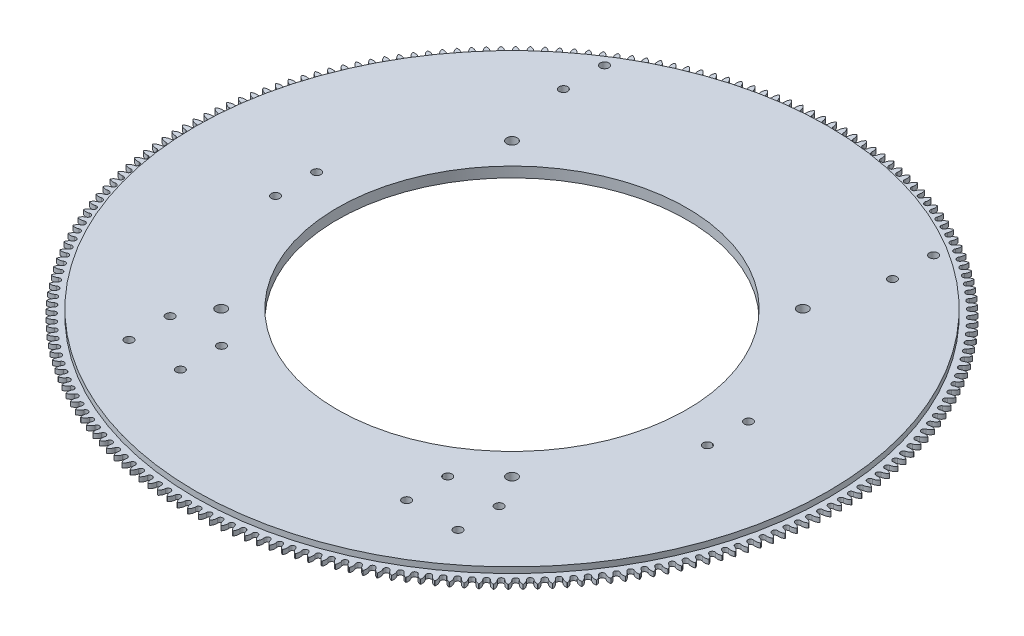
SolidWorks part; units mm, degrees
material "PC High Viscosity"
ref_plane "Front Plane" through (0, 0, 0) normal (0, 0, 1) x (1, 0, 0)
ref_plane "Top Plane" through (0, 0, 0) normal (0, 1, 0) x (1, 0, 0)
ref_plane "Right Plane" through (0, 0, 0) normal (1, 0, 0) x (0, 0, -1)
sketch "Sketch1" plane through (0, 0, 0) normal (0, 1, 0) x (1, 0, 0)
  line L0 (0, 0) -> (0, -95.25) construction
  line L1 (0, -95.25) -> (82.55, -95.25) construction
  line L2 (82.55, -95.25) -> (82.55, -146.0008) construction
  line L3 (82.55, -95.25) -> (88.9, -95.25) construction
  line L4 (88.9, -95.25) -> (88.9, -146.0008) construction
  line L5 (69.85, -109.5375) -> (69.85, -134.9375) construction
  line L6 (101.6, -109.5375) -> (101.6, -134.9375) construction
  line L7 (69.85, -109.5375) -> (101.6, -109.5375) construction
  line L8 (0, 0) -> (89.8026, -89.8026) construction
  line L9 (0, 0) -> (0, 133.35) construction
  line L10 (0, 133.35) -> (101.6, 133.35) construction
  line L11 (101.6, 133.35) -> (101.6, 158.75) construction
  line L12 (0, 0) -> (89.8026, 89.8026) construction
  line L13 (0, 0) -> (133.35, 0) construction
  line L14 (133.35, 0) -> (133.35, -12.7) construction
  line L15 (133.35, 0) -> (133.35, 12.7) construction
  line L16 (101.6, -134.9375) -> (118.4058, -157.2577) construction
  line L17 (101.6, -134.9375) -> (0, 0) construction
  circle A0 centre (0, 0) radius 107.95
  circle A1 centre (69.85, -109.5375) radius 2.6289
  circle A2 centre (69.85, -134.9375) radius 2.6289
  circle A3 centre (101.6, -109.5375) radius 2.6289
  circle A4 centre (101.6, -134.9375) radius 2.6289
  circle A5 centre (89.8026, -89.8026) radius 3.2639
  circle A6 centre (101.6, 133.35) radius 2.6289
  circle A7 centre (101.6, 158.75) radius 2.6289
  circle A10 centre (89.8026, 89.8026) radius 3.2639
  circle A11 centre (133.35, -12.7) radius 2.6289
  circle A12 centre (133.35, 12.7) radius 2.6289
  circle A13 centre (0, 0) radius 196.85
  circle A14 centre (-69.85, -134.9375) radius 2.6289
  circle A15 centre (-101.6, -134.9375) radius 2.6289
  circle A16 centre (-101.6, -109.5375) radius 2.6289
  circle A17 centre (-89.8026, -89.8026) radius 3.2639
  circle A18 centre (-69.85, -109.5375) radius 2.6289
  circle A19 centre (-133.35, -12.7) radius 2.6289
  circle A20 centre (-133.35, 12.7) radius 2.6289
  circle A21 centre (-89.8026, 89.8026) radius 3.2639
  circle A22 centre (-101.6, 158.75) radius 2.6289
  circle A23 centre (-101.6, 133.35) radius 2.6289
  dimension "D1" = 82.55
  dimension "D4" = 12.7
  dimension "D5" = 5.2578
  dimension "D7" = 5.2578
  dimension "D8" = 25.4
  dimension "D9" = 5.2578
  dimension "D10" = 5.2578
  dimension "D15" = 6.5278
  dimension "D18" = 5.2578
  dimension "D20" = 5.2578
  dimension "D21" = 127
  dimension "D22" = 6.5278
  dimension "D25" = 5.2578
  dimension "D26" = 5.2578
  dimension "D28" = 393.7
  dimension "D29" = 215.9
  dimension "D19" = 25.4
  dimension "D2" = 95.25
  dimension "D3" = 6.35
  dimension "D6" = 25.4
  dimension "D11" = 14.2875
  dimension "D12" = 12.7
  dimension "D13" = 127
  dimension "D14" = 45
  dimension "D16" = 101.6
  dimension "D17" = 228.6
  dimension "D23" = 12.7
  dimension "D24" = 12.7
  dimension "D27" = 133.35
extrude "Boss-Extrude1" add sketch "Sketch1" along normal blind 6.35
ref_plane "Plane1" through (0, 0, 0) normal (1, 0, 0) x (0, 0, -1)
sketch "Sketch2" plane through (0, 6.35, 0) normal (0, 1, 0) x (1, 0, 0)
  line L0 (0, 200.1139) -> (-6.3492, 200.0132) construction
  line L1 (-3.1746, 200.0635) -> (-3.1746, 203.4776) construction
  line L2 (0, 200.1139) -> (0, 198.4629) construction
  circle A0 centre (0, 0) radius 200.1139 construction
  arc A1 (-1.6508, 200.0877) -> (0, 198.4629) centre (0, 200.1139) ccw
  arc A2 (-1.6508, 200.0877) -> (-3.1746, 203.4776) centre (-6.3492, 200.0132) ccw
  dimension "D1" = 400.2278
  dimension "D3" = 3.302
  dimension "D2" = 6.35
sketch "Sketch3" plane through (0, 6.35, 0) normal (0, 1, 0) x (1, 0, 0)
  circle A0 centre (0, 0) radius 203.5024
  circle A1 centre (0, 0) radius 196.85 construction
  circle A2 centre (0, 0) radius 196.85
extrude "Boss-Extrude2" add sketch "Sketch3" against normal up to surface (6.35 mm away) up to face at (0, 0, 196.85)
sketch "Sketch4" plane through (0, 6.35, 0) normal (0, 1, 0) x (1, 0, 0)
  line L0 (0, 0) -> (0, 200.1139) construction
  arc A0 (-1.6508, 200.0877) -> (-3.1746, 203.4776) centre (-6.3492, 200.0132) ccw construction
  arc A1 (-1.6508, 200.0877) -> (0, 198.4629) centre (0, 200.1139) ccw construction
  arc A2 (-1.6508, 200.0877) -> (-3.1746, 203.4776) centre (-6.3492, 200.0132) ccw
  arc A3 (-1.6508, 200.0877) -> (1.6508, 200.0877) centre (0, 200.1139) ccw
  arc A4 (1.6508, 200.0877) -> (3.1746, 203.4776) centre (6.3492, 200.0132) cw
  arc A5 (-3.1746, 203.4776) -> (3.1746, 203.4776) centre (0, 0) cw
  circle M23 centre (0, 0) radius 203.5024
extrude "Cut-Extrude1" cut sketch "Sketch4" against normal through all contours A3 A4 A2 M23 region at (0, 6.35, -201.408)
pattern_circular "CirPattern1" count 198 over 360 about axis through (0, -575.5917, 0) along (0, 1, 0) of "Cut-Extrude1"
sketch "Sketch6" plane through (0, 6.35, 0) normal (0, 1, 0) x (1, 0, 0)
  circle A0 centre (0, 0) radius 196.85 construction
  circle A1 centre (0, 0) radius 196.85 construction
  circle A2 centre (0, 0) radius 254
  circle A3 centre (0, 0) radius 195.2625
  dimension "D1" = 508
  dimension "D2" = 1.5875
extrude "Cut-Extrude2" cut sketch "Sketch6" against normal blind 3.556
equation "\"Number of Teeth\"= 198"
equation "\"Pitch\"= 0.25in"
equation "\"Pitch Diameter\"= \"Pitch\" / sin ( ( 180 / \"Number of Teeth\" ) )"
equation "\"Roller pin diameter\"= .13in"
equation "\"Seating curve diameter\"= 1.005 * \"Roller pin diameter\" + 0.003in"
equation "\"D1@Sketch2\"=\"Pitch Diameter\""
equation "\"D2@Sketch2\"=\"Pitch\""
equation "\"D3@Sketch2\"=\"Roller pin diameter\""
equation "\"D1@CirPattern1\"=\"Number of Teeth\""
